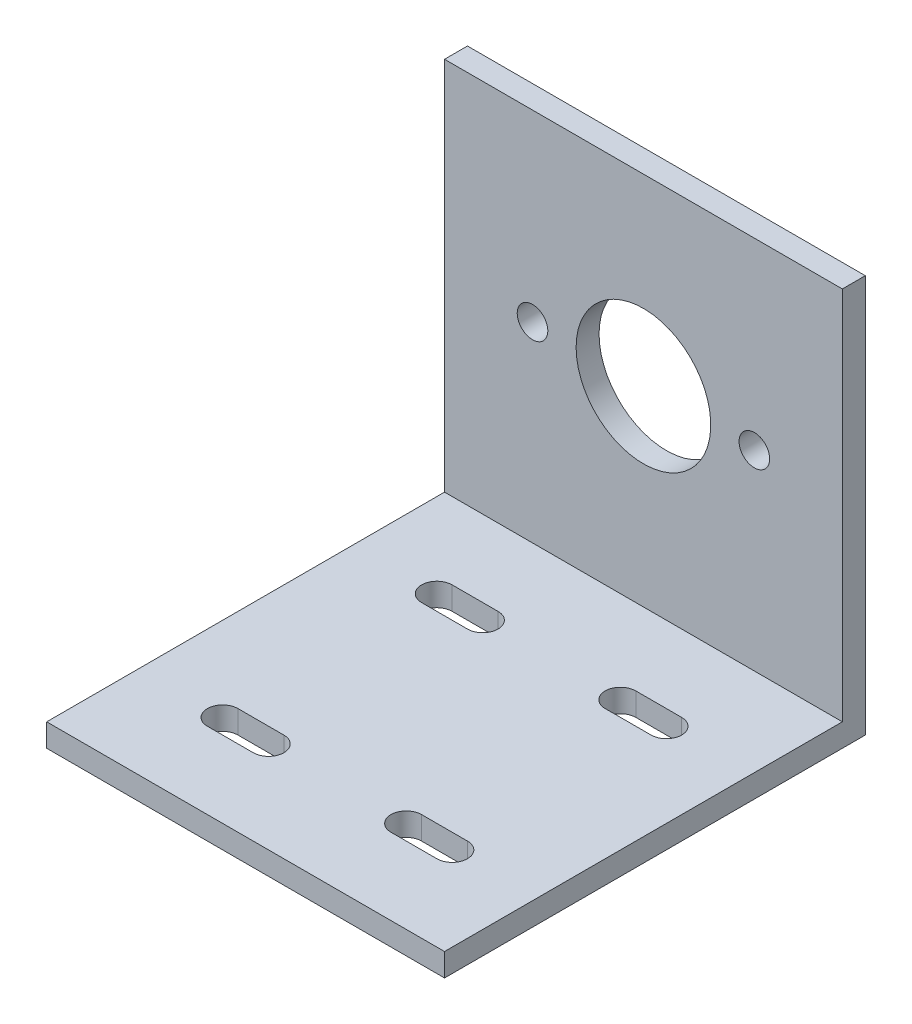
SolidWorks part; units mm, degrees
ref_plane "前基準面" through (0, 0, 0) normal (0, 0, 1) x (1, 0, 0)
ref_plane "上基準面" through (0, 0, 0) normal (0, 1, 0) x (1, 0, 0)
ref_plane "右基準面" through (0, 0, 0) normal (1, 0, 0) x (0, 0, -1)
sketch "草圖1" plane through (0, 0, 0) normal (0, 1, 0) x (1, 0, 0)
  line L0 (-15, 14) -> (-9, 14) construction
  line L1 (26, 26) -> (-26, 26)
  line L2 (26, 26) -> (26, -26)
  line L3 (26, -26) -> (-26, -26)
  line L4 (-26, 26) -> (-26, -26)
  line L5 (0, -26) -> (0, 26) construction
  line L6 (26, 0) -> (-26, 0) construction
  line L7 (-15, 16) -> (-9, 16)
  line L8 (-15, 12) -> (-9, 12)
  line L9 (15, 14) -> (9, 14) construction
  line L10 (15, 16) -> (9, 16)
  line L11 (15, 12) -> (9, 12)
  line L12 (15, -14) -> (9, -14) construction
  line L13 (15, -16) -> (9, -16)
  line L14 (15, -12) -> (9, -12)
  line L15 (-15, -14) -> (-9, -14) construction
  line L16 (-15, -16) -> (-9, -16)
  line L17 (-15, -12) -> (-9, -12)
  arc A0 (-15, 16) -> (-15, 12) centre (-15, 14) ccw
  arc A1 (-9, 12) -> (-9, 16) centre (-9, 14) ccw
  arc A2 (15, 16) -> (15, 12) centre (15, 14) cw
  arc A3 (9, 12) -> (9, 16) centre (9, 14) cw
  arc A4 (15, -16) -> (15, -12) centre (15, -14) ccw
  arc A5 (9, -12) -> (9, -16) centre (9, -14) ccw
  arc A6 (-15, -16) -> (-15, -12) centre (-15, -14) cw
  arc A7 (-9, -12) -> (-9, -16) centre (-9, -14) cw
  point P0 (0, 0)
  point P6 (-12, 14)
  point P14 (-7, 14)
  point P15 (7, 14)
  point P16 (-17, 14)
  point P19 (12, 14)
  point P26 (12, -14)
  point P33 (-12, -14)
  point P38 (9, -14)
  point P39 (12, -12)
  point P40 (14.3389, -11.2348)
  point P41 (17.4341, -11.3987)
  point P42 (0, 0)
  point P43 (-15, -10.7433)
  point P44 (12, 11.7765)
  point P45 (0, 0)
  point P46 (0, 0)
  dimension "D3" = 4
  dimension "D1" = 52
  dimension "D2" = 52
  dimension "D4" = 10
  dimension "D5" = 24
  dimension "D6" = 14
  dimension "D7" = 10
extrude "填料-伸長1" add sketch "草圖1" along normal blind 3
sketch "草圖2" plane through (0, 0, -26) normal (0, 0, -1) x (-1, 0, 0)
  line L0 (-26, 3) -> (-26, 0) construction
  line L1 (26, 0) -> (-26, 0)
  line L2 (26, 0) -> (26, 52)
  line L3 (26, 52) -> (-26, 52)
  line L4 (-26, 0) -> (-26, 52)
  line L5 (0, 58.3104) -> (0, -5.5003) construction
  circle A0 centre (-14.5, 28) radius 2
  circle A1 centre (14.5, 28) radius 2
  circle A2 centre (0, 28) radius 8.8
  point P14 (14.5, 30)
  point P17 (-12.5, 28)
  point P18 (12.5, 28)
  dimension "D2" = 4
  dimension "D5" = 17.6
  dimension "D1" = 52
  dimension "D3" = 25
  dimension "D4" = 22
extrude "填料-伸長2" add sketch "草圖2" along normal blind 3
